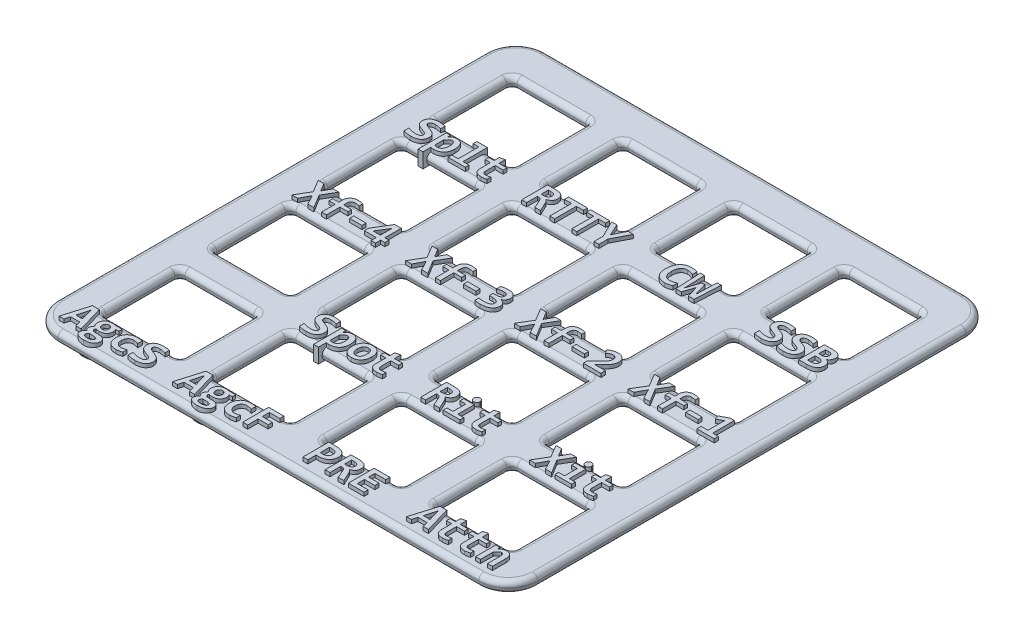
SolidWorks part; units mm, degrees
ref_plane "Front" through (0, 0, 0) normal (0, 0, 1) x (1, 0, 0)
ref_plane "Top" through (0, 0, 0) normal (0, 1, 0) x (1, 0, 0)
ref_plane "Right" through (0, 0, 0) normal (1, 0, 0) x (0, 0, -1)
sketch "Sketch1" plane through (0, 0, 0) normal (0, 1, 0) x (1, 0, 0)
  line L1 (-14.8807, -14.5355) -> (42.1193, -14.5355)
  line L2 (-18.8807, -18.5355) -> (-18.8807, -76.5355)
  line L3 (-14.8807, -80.5355) -> (42.1193, -80.5355)
  line L4 (46.1193, -18.5355) -> (46.1193, -76.5355)
  arc A0 (-14.8807, -14.5355) -> (-18.8807, -18.5355) centre (-14.8807, -18.5355) ccw
  arc A1 (46.1193, -18.5355) -> (42.1193, -14.5355) centre (42.1193, -18.5355) ccw
  arc A2 (42.1193, -80.5355) -> (46.1193, -76.5355) centre (42.1193, -76.5355) ccw
  arc A3 (-18.8807, -76.5355) -> (-14.8807, -80.5355) centre (-14.8807, -76.5355) ccw
  dimension "D1" = 65
  dimension "D2" = 66
extrude "main" add sketch "Sketch1" along normal blind 1.5
sketch "Sketch2" plane through (0, 1.5, 0) normal (0, 1, 0) x (1, 0, 0)
  line L0 (42.1193, -14.5355) -> (-14.8807, -14.5355) construction
  line L1 (-14.2307, -19.6855) -> (-3.5307, -19.6855)
  line L2 (-14.2307, -19.6855) -> (-14.2307, -30.3855)
  line L3 (-14.2307, -30.3855) -> (-3.5307, -30.3855)
  line L4 (-3.5307, -19.6855) -> (-3.5307, -30.3855)
  line L5 (-18.8807, -18.5355) -> (-18.8807, -76.5355) construction
  point P4 (-8.8807, -19.6855)
  dimension "D1" = 5.15
  dimension "D2" = 4.65
  dimension "D3" = 10.7
  dimension "D4" = 10.7
extrude "button hole 1" cut sketch "Sketch2" against normal through all
fillet "button fillet" radius 0.7 12 edges at (-8.8807, 0, 30.3855) (-8.8807, 1.5, 30.3855) (-8.8807, 0, 19.6855) (-8.8807, 1.5, 19.6855) (-3.5307, 0.75, 30.3855) (-3.5307, 0, 25.0355) (-3.5307, 0.75, 19.6855) (-3.5307, 1.5, 25.0355) (-14.2307, 0.75, 19.6855) (-14.2307, 0, 25.0355) (-14.2307, 0.75, 30.3855) (-14.2307, 1.5, 25.0355)
pattern_linear "buttons by 16" count 4 spacing 15 along (1, 0, 0) count 4 spacing 15 along (0, 0, 1) of "button fillet", "button hole 1"
fillet "outer edge fillet" radius 0.7 16 edges at (13.6193, 1.5, 14.5355) (13.6193, 0, 14.5355) (46.1193, 1.5, 47.5355) (46.1193, 0, 47.5355) (13.6193, 1.5, 80.5355) (13.6193, 0, 80.5355) (-18.8807, 1.5, 47.5355) (-18.8807, 0, 47.5355) (44.9477, 1.5, 15.7071) (44.9477, 1.5, 79.364) (-17.7092, 1.5, 79.364) (-17.7092, 1.5, 15.7071) (44.9477, 0, 15.7071) (44.9477, 0, 79.364) (-17.7092, 0, 79.364) (-17.7092, 0, 15.7071)
sketch "Lettering" plane through (0, 0, 0) normal (0, 1, 0) x (1, 0, 0)
  line L0 (45.4193, -49.1355) -> (-18.1807, -49.1355) construction
  line L1 (45.4783, -79.1355) -> (-16.5217, -79.1355) construction
  line L2 (45.4193, -76.5355) -> (45.4193, -18.5355) construction
  line L3 (-18.1807, -18.5355) -> (-18.1807, -76.5355) construction
  line L5 (45.4193, -64.1355) -> (-18.1807, -64.1355) construction
  line L6 (45.4193, -76.5355) -> (45.4193, -18.5355) construction
  line L7 (-18.1807, -18.5355) -> (-18.1807, -76.5355) construction
  line L8 (45.4193, -34.1355) -> (-18.1807, -34.1355) construction
  line L11 (-14.8807, -80.5355) -> (42.1193, -80.5355) construction
  text T0 "SSB" font "Consolas" height 3.5
  text T1 "CW" font "Consolas" height 3.5
  text T2 "RTTY" font "Consolas" height 3.5
  text T3 "Splt" font "Consolas" height 3.5
  text T4 "Xit" font "Consolas" height 3.5
  text T5 "Rit" font "Consolas" height 3.5
  text T7 "Spot" font "Consolas" height 3.5
  text T8 "Attn" font "Consolas" height 3.5
  text T9 "PRE" font "Consolas" height 3.5
  text T10 "AgcF" font "Consolas" height 3.5
  text T11 "AgcS" font "Consolas" height 3.5
  text T12 "Xf-1" font "Consolas" height 3.5
  text T13 "Xf-2" font "Consolas" height 3.5
  text T14 "Xf-3" font "Consolas" height 3.5
  text T15 "Xf-4" font "Consolas" height 3.5
  dimension "D1" = 46.4
  dimension "D2" = 16.4
  dimension "D3" = 1.4
  dimension "D4" = 31.4
extrude "lettering boss" add sketch "Lettering" along normal offset from surface (2 mm away) 0.5 up to face at (13.6193, 1.5, 47.5355) offset beyond the face yes
